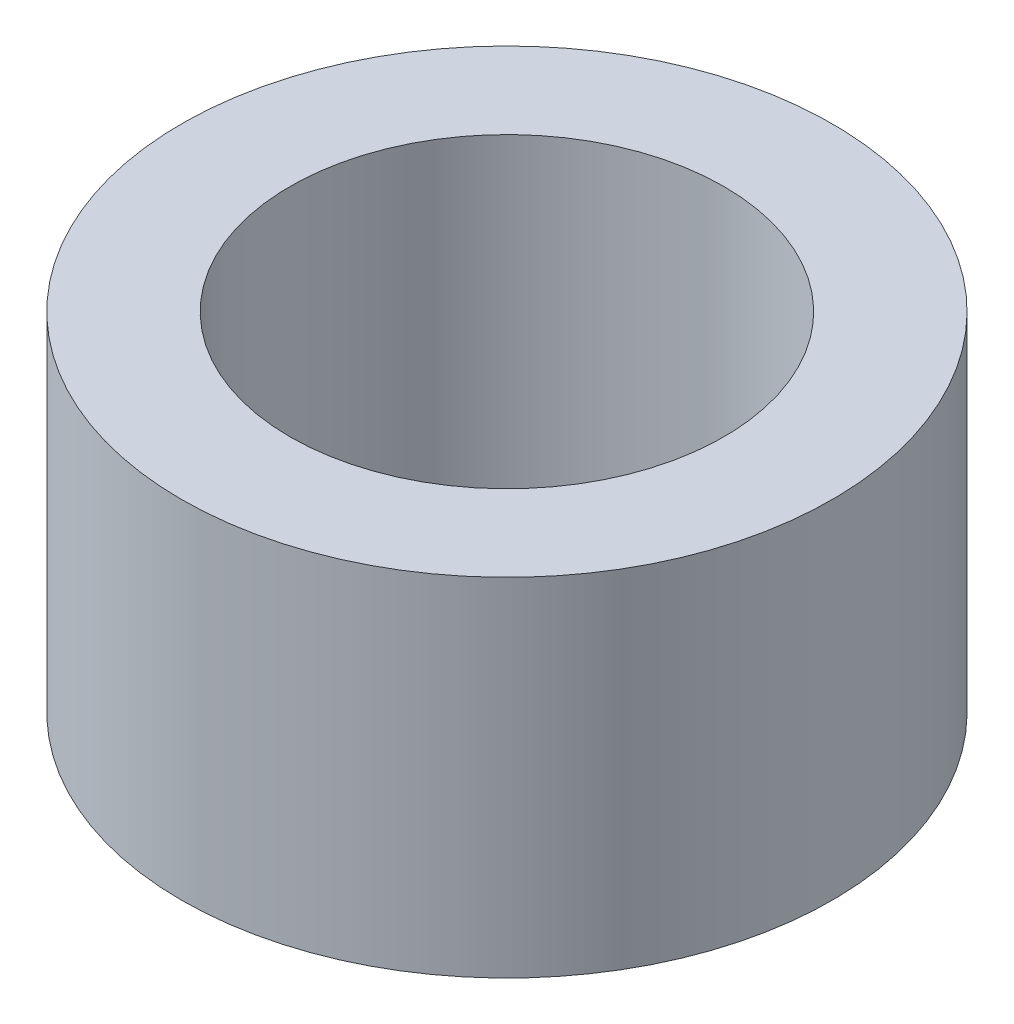
SolidWorks part; units mm, degrees
ref_plane "Front Plane" through (0, 0, 0) normal (0, 0, 1) x (1, 0, 0)
ref_plane "Top Plane" through (0, 0, 0) normal (0, 1, 0) x (1, 0, 0)
ref_plane "Right Plane" through (0, 0, 0) normal (1, 0, 0) x (0, 0, -1)
sketch "Sketch1" plane through (0, 0, 0) normal (0, 1, 0) x (1, 0, 0)
  circle A0 centre (0, 0) radius 7.5
  dimension "D1" = 15
extrude "Boss-Extrude1" add sketch "Sketch1" along normal blind 4
sketch "Sketch2" plane through (0, 4, 0) normal (0, 1, 0) x (1, 0, 0)
  circle A0 centre (0, 0) radius 5
  dimension "D1" = 10
extrude "Cut-Extrude1" cut sketch "Sketch2" against normal blind 10
sketch "Sketch3" plane through (0, 4, 0) normal (0, 1, 0) x (1, 0, 0)
  circle A0 centre (0, 0) radius 7.5
  circle A1 centre (0, 0) radius 5
extrude "Boss-Extrude2" add sketch "Sketch3" along normal blind 4
